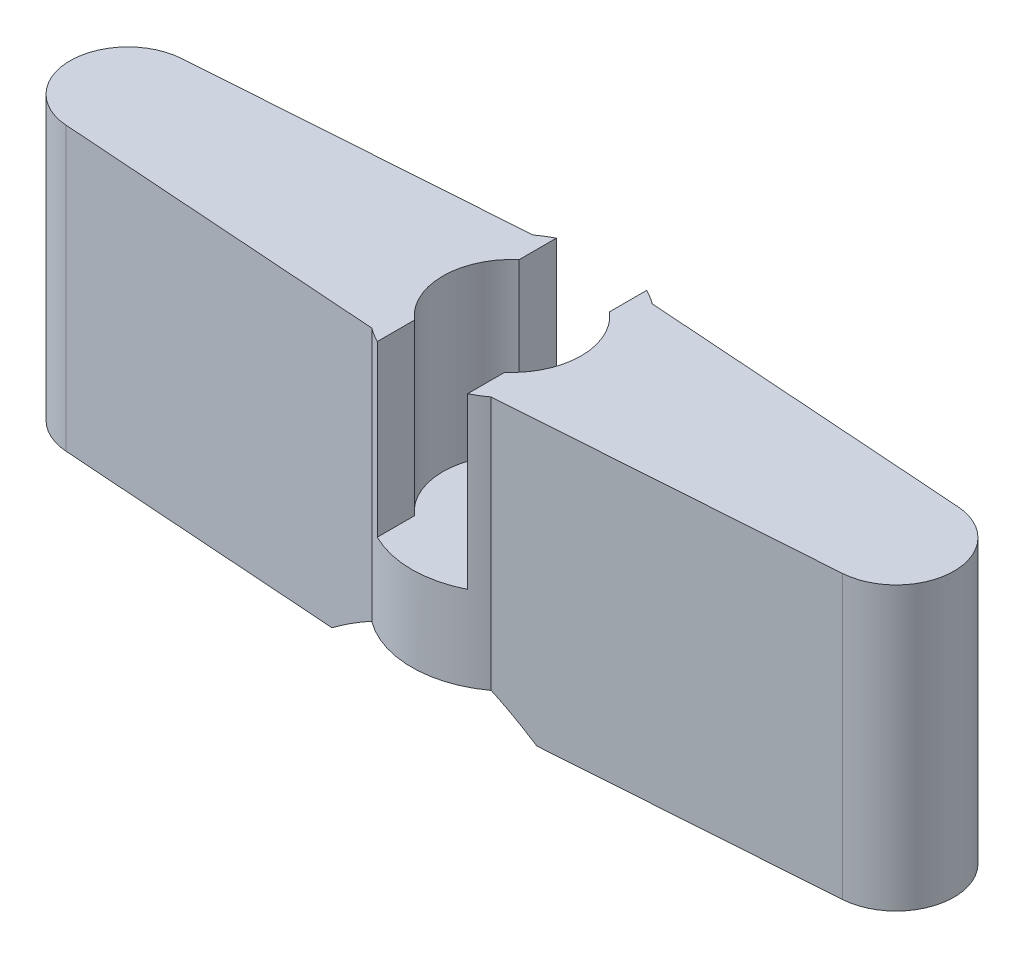
SolidWorks part; units mm, degrees
ref_plane "Front Plane" through (0, 0, 0) normal (0, 0, 1) x (1, 0, 0)
ref_plane "Top Plane" through (0, 0, 0) normal (0, 1, 0) x (1, 0, 0)
ref_plane "Right Plane" through (0, 0, 0) normal (1, 0, 0) x (0, 0, -1)
sketch "Sketch2" plane through (0, 0, 0) normal (0, 1, 0) x (1, 0, 0)
  line L0 (0, 0) -> (-13.6, 0) construction
  line L1 (-13.7421, -2.0451) -> (-2.1121, -2.8534)
  line L2 (-13.7525, -2.1947) -> (-2.1656, -3) construction
  line L3 (-13.7525, 2.1947) -> (-2.1656, 3) construction
  line L4 (0, 3.7) -> (0, -3.7) construction
  line L5 (13.7525, 2.1947) -> (2.1656, 3) construction
  line L6 (13.7525, -2.1947) -> (2.1656, -3) construction
  line L7 (13.7421, -2.0451) -> (2.1121, -2.8534)
  line L8 (13.7421, 2.0451) -> (2.1121, 2.8534)
  line L9 (-13.7421, 2.0451) -> (-2.1121, 2.8534)
  arc A0 (-13.7525, -2.1947) -> (-13.7525, 2.1947) centre (-13.6, 0) cw construction
  arc A2 (-2.1656, -3) -> (2.1656, -3) centre (0, 0) ccw construction
  arc A3 (13.7525, -2.1947) -> (13.7525, 2.1947) centre (13.6, 0) ccw construction
  arc A4 (-2.1656, 3) -> (-3.7, 0) centre (0, 0) ccw construction
  arc A5 (-3.7, 0) -> (-2.1656, -3) centre (0, 0) ccw construction
  arc A6 (2.1656, 3) -> (-2.1656, 3) centre (0, 0) ccw construction
  arc A7 (2.1656, -3) -> (2.1656, 3) centre (0, 0) ccw construction
  arc A8 (-2.1121, -2.8534) -> (2.1121, -2.8534) centre (0, 0) ccw
  arc A9 (13.7421, -2.0451) -> (13.7421, 2.0451) centre (13.6, 0) ccw
  arc A10 (2.1121, 2.8534) -> (-2.1121, 2.8534) centre (0, 0) ccw
  arc A11 (-13.7421, -2.0451) -> (-13.7421, 2.0451) centre (-13.6, 0) cw
  point P1 (-15.8, 0)
  point P30 (0, 0)
  dimension "D2" = 7.4
  dimension "D5" = 2.2
  dimension "D1" = 15.8
  dimension "D3" = 0.15
  dimension "D4" = 6
extrude "Boss-Extrude1" add sketch "Sketch2" along normal blind 10
sketch "Sketch3" plane through (0, 0, 0) normal (0, -1, 0) x (1, 0, 0)
  arc A0 (-2.1121, -2.8534) -> (2.1121, -2.8534) centre (0, 0) ccw construction
  arc A1 (2.1121, 2.8534) -> (-2.1121, 2.8534) centre (0, 0) ccw construction
  arc A2 (-2.1121, 2.8534) -> (2.1121, 2.8534) centre (0, 0) ccw
  arc A3 (2.1121, 2.8534) -> (-2.1121, 2.8534) centre (0, 0) ccw
extrude "Cut-Extrude1" cut sketch "Sketch3" against normal blind 1
sketch "Shaft Key" plane through (0, 10, 0) normal (0, 1, 0) x (1, 0, 0)
  line L0 (1.5, -1.809) -> (1.5, -5.35) construction
  line L7 (1.5, -5.35) -> (-1.5, -5.35) construction
  line L8 (-1.5, -5.35) -> (-1.5, -1.809) construction
  line L9 (0, -2.35) -> (0, -5.35) construction
  line L10 (-2.35, 0) -> (2.35, 0) construction
  line L11 (-1.5, 5.35) -> (-1.5, 1.809) construction
  line L12 (1.5, 5.35) -> (-1.5, 5.35) construction
  line L13 (1.5, 1.809) -> (1.5, 5.35) construction
  line L14 (0, 0) -> (0, -2.35) construction
  line L15 (1.6, -1.8554) -> (1.6, -5.45)
  line L16 (1.6, -5.45) -> (-1.6, -5.45)
  line L17 (-1.6, -5.45) -> (-1.6, -1.8554)
  line L18 (-1.6, 5.45) -> (-1.6, 1.8554)
  line L19 (1.6, 5.45) -> (-1.6, 5.45)
  line L20 (1.6, 1.8554) -> (1.6, 5.45)
  arc A0 (1.5, -1.809) -> (1.5, 1.809) centre (0, 0) ccw construction
  arc A1 (-1.5, -1.809) -> (0, -2.35) centre (0, 0) ccw construction
  arc A2 (0, -2.35) -> (1.5, -1.809) centre (0, 0) ccw construction
  arc A3 (-1.5, 1.809) -> (-1.5, -1.809) centre (0, 0) ccw construction
  arc A4 (1.5, 1.809) -> (-1.5, 1.809) centre (0, 0) ccw construction
  arc A5 (-1.6, 1.8554) -> (-1.6, -1.8554) centre (0, 0) ccw
  arc A6 (1.6, -1.8554) -> (1.6, 1.8554) centre (0, 0) ccw
  point P11 (0, 0)
  dimension "D1" = 4.7
  dimension "D2" = 3
  dimension "D3" = 3
  dimension "D4" = 0.1
chamfer "Chamfer1" distance 1 angle 45 2 edges at (3.55, 0, 0) (-3.55, 0, 0)
extrude "Cut-Extrude2" cut sketch "Shaft Key" against normal blind 6
